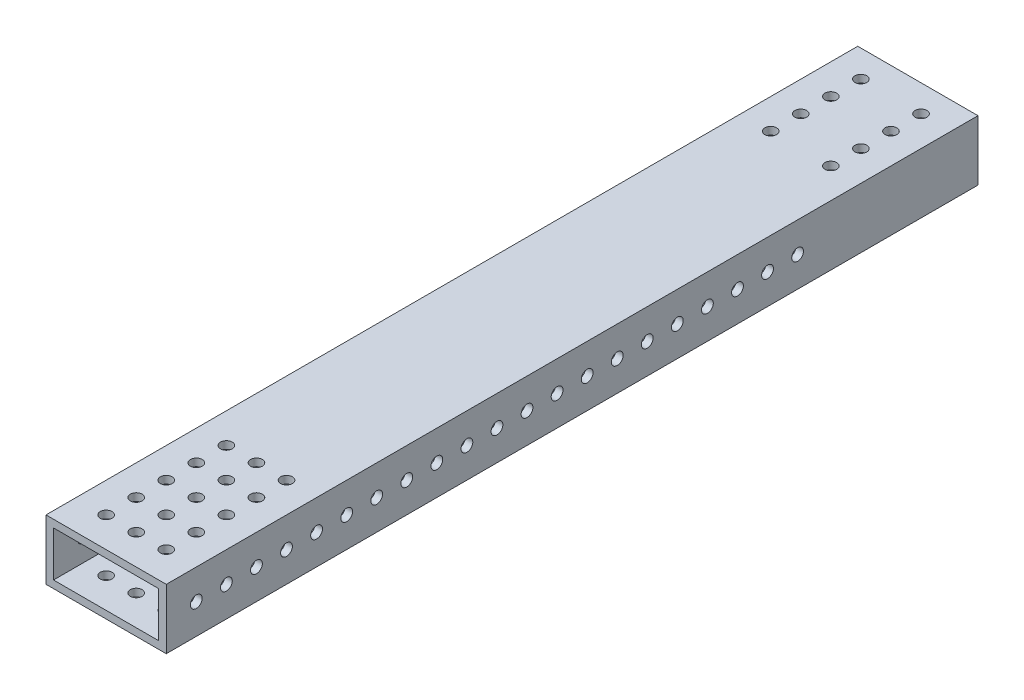
SolidWorks part; units mm, degrees
material "6061-T6 (SS)"
ref_plane "Front Plane" through (0, 0, 0) normal (0, 0, 1) x (1, 0, 0)
ref_plane "Top Plane" through (0, 0, 0) normal (0, 1, 0) x (1, 0, 0)
ref_plane "Right Plane" through (0, 0, 0) normal (1, 0, 0) x (0, 0, -1)
sketch "Sketch1" plane through (0, 0, 0) normal (0, 1, 0) x (1, 0, 0)
  line L1 (0, 0) -> (50.8, 0)
  line L2 (0, 0) -> (0, 342.9)
  line L3 (0, 342.9) -> (50.8, 342.9)
  line L4 (50.8, 0) -> (50.8, 342.9)
  dimension "D1" = 50.8
  dimension "D2" = 342.9
extrude "Boss-Extrude1" add sketch "Sketch1" along normal blind 25.4
shell "Shell1" thickness 3.175 removed face at (25.4, 12.7, -342.9) removed face at (25.4, 12.7, 0)
sketch "Sketch2" plane through (0, 0, 0) normal (-1, 0, 0) x (0, 0, 1)
  line L0 (0, 12.7) -> (-342.9, 12.7) construction
  line L1 (0, 25.4) -> (0, 0) construction
  line L2 (-342.9, 25.4) -> (-342.9, 0) construction
  circle A0 centre (-12.7, 12.7) radius 2.4892
  circle A1 centre (-25.4, 12.7) radius 2.4892
  circle A2 centre (-38.1, 12.7) radius 2.4892
  circle A3 centre (-50.8, 12.7) radius 2.4892
  circle A4 centre (-63.5, 12.7) radius 2.4892
  circle A5 centre (-76.2, 12.7) radius 2.4892
  circle A6 centre (-88.9, 12.7) radius 2.4892
  circle A7 centre (-101.6, 12.7) radius 2.4892
  circle A8 centre (-114.3, 12.7) radius 2.4892
  circle A9 centre (-127, 12.7) radius 2.4892
  circle A10 centre (-139.7, 12.7) radius 2.4892
  circle A11 centre (-152.4, 12.7) radius 2.4892
  circle A12 centre (-165.1, 12.7) radius 2.4892
  circle A13 centre (-177.8, 12.7) radius 2.4892
  circle A14 centre (-190.5, 12.7) radius 2.4892
  circle A15 centre (-203.2, 12.7) radius 2.4892
  circle A16 centre (-215.9, 12.7) radius 2.4892
  circle A17 centre (-228.6, 12.7) radius 2.4892
  circle A18 centre (-241.3, 12.7) radius 2.4892
  circle A19 centre (-254, 12.7) radius 2.4892
  circle A20 centre (-266.7, 12.7) radius 2.4892
  dimension "D1" = 4.9784
  dimension "D2" = 12.7
  dimension "D3" = 12.7
  dimension "D4" = 21
extrude "Cut-Extrude1" cut sketch "Sketch2" against normal through all
sketch "Sketch3" plane through (0, 25.4, 0) normal (0, 1, 0) x (1, 0, 0)
  circle A0 centre (12.7, 293.4246) radius 2.4892 construction
  circle A1 centre (38.1, 293.4246) radius 2.4892 construction
  circle A2 centre (38.1, 306.1246) radius 2.4892 construction
  circle A3 centre (12.7, 306.1246) radius 2.4892 construction
  circle A4 centre (12.7, 318.8246) radius 2.4892 construction
  circle A5 centre (38.1, 318.8246) radius 2.4892 construction
  circle A6 centre (38.1, 331.5246) radius 2.4892 construction
  circle A7 centre (12.7, 331.5246) radius 2.4892 construction
  circle A8 centre (12.7, 293.4246) radius 2.4892
  circle A9 centre (38.1, 293.4246) radius 2.4892
  circle A10 centre (38.1, 306.1246) radius 2.4892
  circle A11 centre (12.7, 306.1246) radius 2.4892
  circle A12 centre (12.7, 318.8246) radius 2.4892
  circle A13 centre (38.1, 318.8246) radius 2.4892
  circle A14 centre (38.1, 331.5246) radius 2.4892
  circle A15 centre (12.7, 331.5246) radius 2.4892
  circle A16 centre (38.1, 63.5) radius 2.4892 construction
  circle A17 centre (25.4, 63.5) radius 2.4892 construction
  circle A18 centre (12.7, 63.5) radius 2.4892 construction
  circle A19 centre (12.7, 50.8) radius 2.4892 construction
  circle A20 centre (25.4, 50.8) radius 2.4892 construction
  circle A21 centre (38.1, 50.8) radius 2.4892 construction
  circle A22 centre (12.7, 38.1) radius 2.4892 construction
  circle A23 centre (25.4, 38.1) radius 2.4892 construction
  circle A24 centre (38.1, 38.1) radius 2.4892 construction
  circle A25 centre (38.1, 25.4) radius 2.4892 construction
  circle A26 centre (25.4, 25.4) radius 2.4892 construction
  circle A27 centre (12.7, 25.4) radius 2.4892 construction
  circle A28 centre (12.7, 12.7) radius 2.4892 construction
  circle A29 centre (25.4, 12.7) radius 2.4892 construction
  circle A30 centre (38.1, 12.7) radius 2.4892 construction
  circle A31 centre (38.1, 63.5) radius 2.4892
  circle A32 centre (25.4, 63.5) radius 2.4892
  circle A33 centre (12.7, 63.5) radius 2.4892
  circle A34 centre (12.7, 50.8) radius 2.4892
  circle A35 centre (25.4, 50.8) radius 2.4892
  circle A36 centre (38.1, 50.8) radius 2.4892
  circle A37 centre (12.7, 38.1) radius 2.4892
  circle A38 centre (25.4, 38.1) radius 2.4892
  circle A39 centre (38.1, 38.1) radius 2.4892
  circle A40 centre (38.1, 25.4) radius 2.4892
  circle A41 centre (25.4, 25.4) radius 2.4892
  circle A42 centre (12.7, 25.4) radius 2.4892
  circle A43 centre (12.7, 12.7) radius 2.4892
  circle A44 centre (25.4, 12.7) radius 2.4892
  circle A45 centre (38.1, 12.7) radius 2.4892
extrude "Cut-Extrude2" cut sketch "Sketch3" against normal through all
